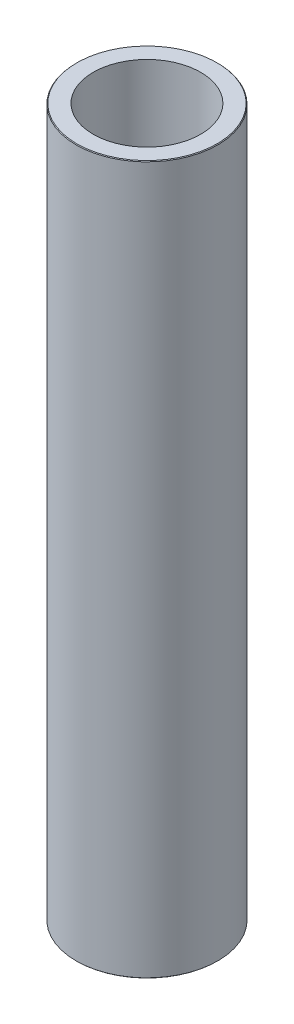
SolidWorks part; units mm, degrees
ref_plane "Front Plane" through (0, 0, 0) normal (0, 0, 1) x (1, 0, 0)
ref_plane "Top Plane" through (0, 0, 0) normal (0, 1, 0) x (1, 0, 0)
ref_plane "Right Plane" through (0, 0, 0) normal (1, 0, 0) x (0, 0, -1)
sketch "Sketch1" plane through (0, 0, 0) normal (0, 1, 0) x (1, 0, 0)
  circle A0 centre (0, 0) radius 60
  dimension "SHAFT_OD" = 120
extrude "Boss-Extrude1" add sketch "Sketch1" along normal blind 600
sketch "Sketch2" plane through (0, 0, 0) normal (0, 1, 0) x (1, 0, 0)
  circle A0 centre (0, 0) radius 45.5461
  dimension "BORE_D" = 91.0922
extrude "Cut-Extrude1" cut sketch "Sketch2" along normal through all
chamfer "Chamfer1" distance 0.5806 angle 42.894 2 edges at (0, 600, 60) (0, 0, 60) first distance on face at (0, 600, 60) first distance on face at (0, 0, 45.5461)
